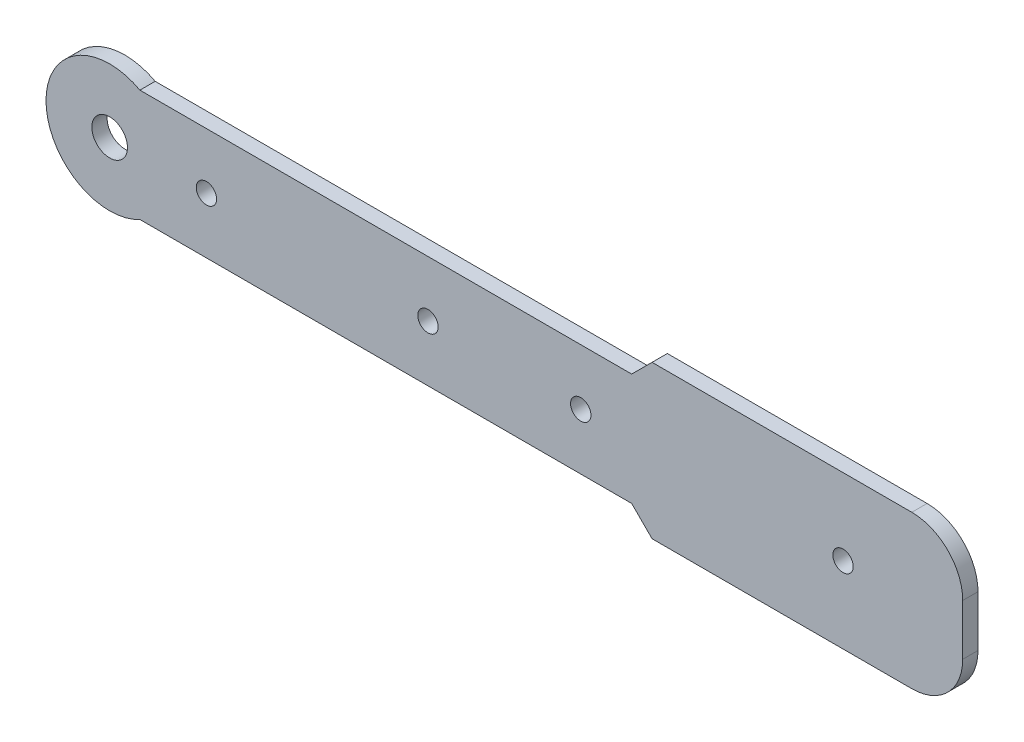
SolidWorks part; units mm, degrees
material "Balsa"
ref_plane "Alzado" through (0, 0, 0) normal (0, 0, 1) x (1, 0, 0)
ref_plane "Planta" through (0, 0, 0) normal (0, 1, 0) x (1, 0, 0)
ref_plane "Vista lateral" through (0, 0, 0) normal (1, 0, 0) x (0, 0, -1)
sketch "Croquis1" plane through (0, 0, 0) normal (0, 0, 1) x (1, 0, 0)
  line L4 (90, -15) -> (90, 15)
  line L9 (-25, 11) -> (25, 11)
  line L10 (25, 15) -> (25, 11)
  line L11 (25, -15) -> (90, -15)
  line L14 (25, -15) -> (25, -11)
  line L15 (-25, -11) -> (25, -11)
  line L16 (25, 15) -> (90, 15)
  line L17 (-25, 11) -> (-71.5628, 11)
  line L19 (-25, -11) -> (-71.5628, -11)
  arc A0 (-71.5628, 11) -> (-71.5628, -11) centre (-77.5, 0) ccw
  point P0 (0, 0)
  point P8 (0, 15)
  dimension "D3" = 50
  dimension "D4" = 12.5
  dimension "D1" = 77.5
  dimension "D2" = 30
  dimension "D5" = 4
  dimension "D6" = 11
extrude "Saliente-Extruir1" add sketch "Croquis1" along normal blind 3
fillet "Redondeo1" radius 10 2 edges at (90, -15, 1.5) (90, 15, 1.5)
chamfer "Chaflán1" distance 4 angle 45 2 edges at (25, -15, 1.5) (25, 15, 1.5)
sketch "Croquis2" plane through (0, 0, 3) normal (0, 0, 1) x (1, 0, 0)
  line L0 (90, -5) -> (90, 5) construction
  line L5 (37.25, 10.25) -> (77.75, -10.25) construction
  line L6 (37.25, -10.25) -> (77.75, 10.25) construction
  line L7 (80, 15) -> (29, 15) construction
  line L8 (57.5, 0) -> (49.6153, 0) construction
  line L9 (49.6153, 0) -> (57.5, 0) construction
  line L10 (57.5, 0) -> (57.5, 5) construction
  circle A4 centre (66.5, 0) radius 2
  point P0 (57.5, 0)
  dimension "D7" = 9
  dimension "D1" = 40.5
  dimension "D2" = 20.5
  dimension "D3" = 32.5
  dimension "D4" = 15
sketch "Croquis3" plane through (0, 0, 3) normal (0, 0, 1) x (1, 0, 0)
  line L0 (-71.5628, -11) -> (25, -11) construction
  circle A0 centre (-77.5, 0) radius 3.5
  arc A1 (-71.5628, 11) -> (-71.5628, -11) centre (-77.5, 0) ccw construction
  circle A2 centre (-58.5, 0) radius 2
  point P5 (-90, 0)
  dimension "D1" = 12.5
  dimension "D2" = 19
  dimension "D3" = 11
extrude "Cortar-Extruir2" cut sketch "Croquis3" against normal up to next
sketch "Croquis4" plane through (0, 0, 3) normal (0, 0, 1) x (1, 0, 0)
  circle A2 centre (-15, 0) radius 2
  circle A3 centre (15, 0) radius 2
  dimension "D1" = 4
  dimension "D2" = 15
  dimension "D3" = 30
extrude "Cortar-Extruir3" cut sketch "Croquis4" against normal up to next
extrude "Cortar-Extruir4" cut sketch "Croquis2" against normal up to next
